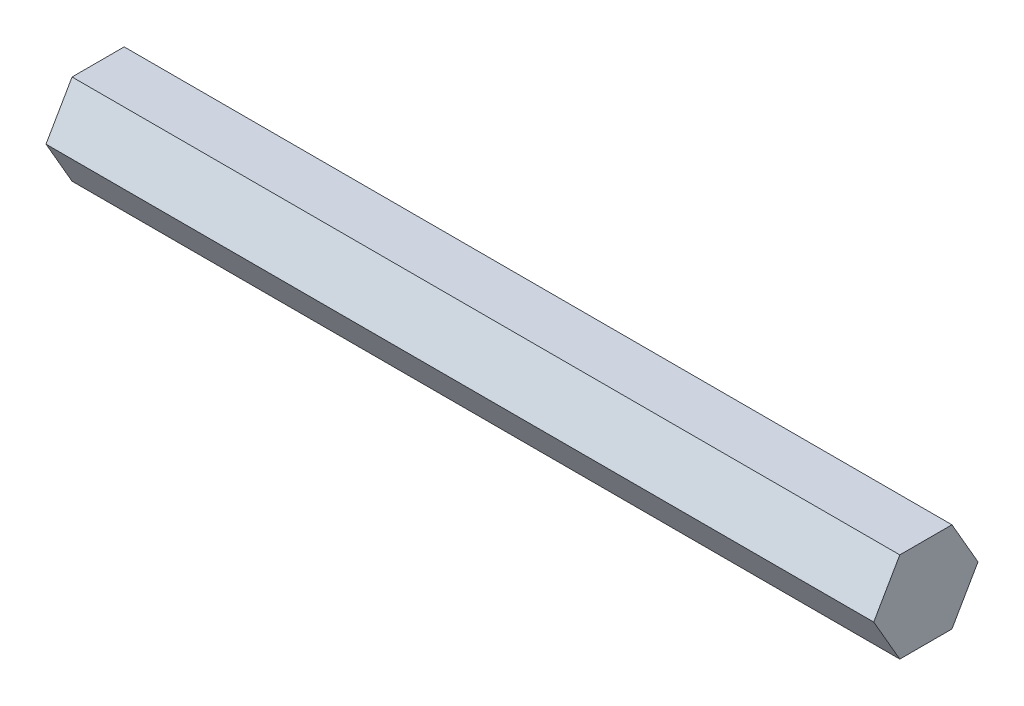
SolidWorks part; units mm, degrees
material "1060 Alloy"
ref_plane "Front Plane" through (0, 0, 0) normal (0, 0, 1) x (1, 0, 0)
ref_plane "Top Plane" through (0, 0, 0) normal (0, 1, 0) x (1, 0, 0)
ref_plane "Right Plane" through (0, 0, 0) normal (1, 0, 0) x (0, 0, -1)
sketch "Sketch1" plane through (0, 0, 0) normal (1, 0, 0) x (0, 0, -1)
  line L1 (6.9282, 0) -> (3.4641, 6)
  line L2 (3.4641, 6) -> (-3.4641, 6)
  line L3 (-3.4641, 6) -> (-6.9282, 0)
  line L4 (-6.9282, 0) -> (-3.4641, -6)
  line L5 (-3.4641, -6) -> (3.4641, -6)
  line L6 (3.4641, -6) -> (6.9282, 0)
  circle A0 centre (0, 0) radius 6 construction
  dimension "D1" = 12
extrude "Boss-Extrude1" add sketch "Sketch1" along normal blind 110
